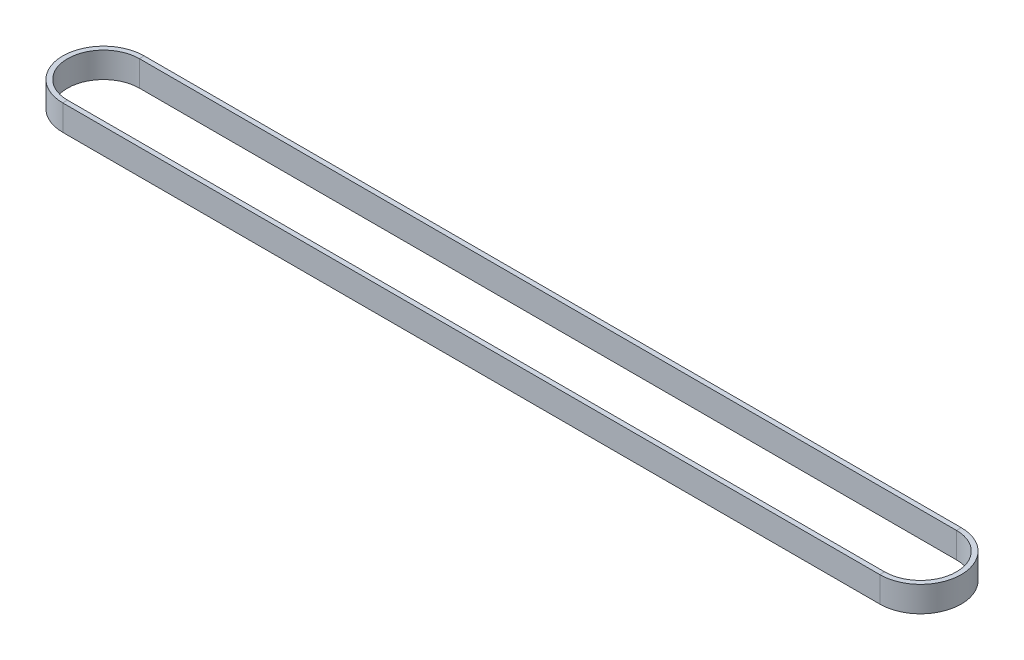
SolidWorks part; units mm, degrees
ref_plane "Front" through (0, 0, 0) normal (0, 0, 1) x (1, 0, 0)
ref_plane "Top" through (0, 0, 0) normal (0, 1, 0) x (1, 0, 0)
ref_plane "Right" through (0, 0, 0) normal (1, 0, 0) x (0, 0, -1)
sketch "Sketch1" plane through (0, 0, 0) normal (0, 1, 0) x (1, 0, 0)
  line L0 (0, 0) -> (325.0052, 0) construction
  line L1 (0, 15.24) -> (325.0052, 15.24)
  line L2 (0, -15.24) -> (325.0052, -15.24)
  arc A0 (0, 15.24) -> (0, -15.24) centre (0, 0) ccw
  arc A1 (325.0052, -15.24) -> (325.0052, 15.24) centre (325.0052, 0) ccw
  point P3 (162.5026, 0)
  dimension "D1" = 325.0052
  dimension "D2" = 30.48
sketch "Sketch2" plane through (0, 0, 0) normal (1, 0, 0) x (0, 0, -1)
  line L1 (-14.2875, -5.08) -> (-16.1925, -5.08)
  line L2 (-14.2875, -5.08) -> (-14.2875, 5.08)
  line L3 (-14.2875, 5.08) -> (-16.1925, 5.08)
  line L4 (-16.1925, -5.08) -> (-16.1925, 5.08)
  line L5 (-14.2875, -5.08) -> (-16.1925, 5.08) construction
  line L6 (-14.2875, 5.08) -> (-16.1925, -5.08) construction
  point P1 (-15.24, 0)
  dimension "D1" = 10.16
  dimension "D2" = 1.905
sweep "Sweep1" add profiles "Sketch2" path "Sketch1"
ref_axis "Axis1" through (0, 0, 0) along (0, 1, 0)
ref_axis "Axis2" through (325.0052, 0, 0) along (0, 1, 0)
